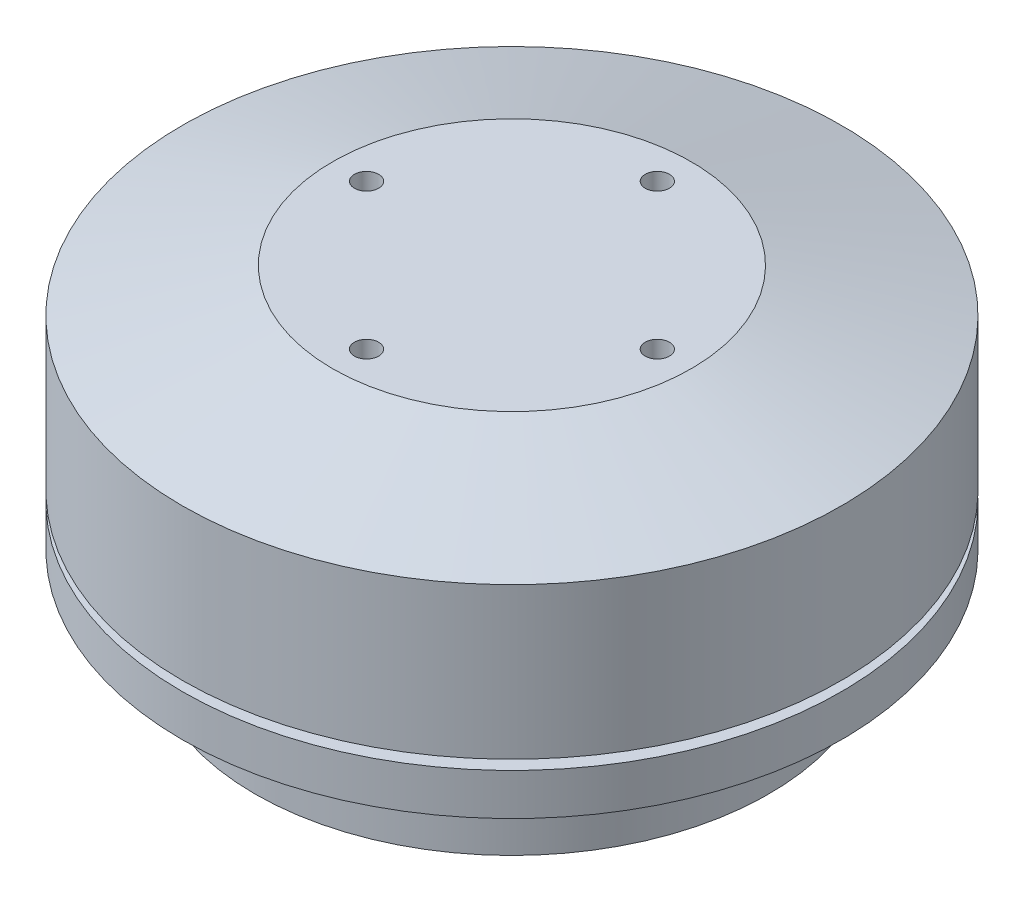
SolidWorks part; units mm, degrees
ref_plane "Спереди" through (0, 0, 0) normal (0, 0, 1) x (1, 0, 0)
ref_plane "Сверху" through (0, 0, 0) normal (0, 1, 0) x (1, 0, 0)
ref_plane "Справа" through (0, 0, 0) normal (1, 0, 0) x (0, 0, -1)
ref_axis "Axis1" through (0, 0, 0) along (0, 1, 0)
sketch "Sketch1" plane through (0, 0, 0) normal (0, 0, 1) x (1, 0, 0)
  line L0 (0, 0) -> (0, -13241.6823) construction
  line L1 (0, 0) -> (0, 34)
  line L2 (0, 34) -> (-18.5, 34)
  line L3 (-18.5, 34) -> (-34, 29.5)
  line L4 (-34, 29.5) -> (-34, 13.9)
  line L5 (-34, 13.9) -> (-32.5205, 13.9)
  line L6 (-32.5205, 13.9) -> (-32.5205, 12.9)
  line L7 (-32.5205, 12.9) -> (-34, 12.9)
  line L8 (-34, 12.9) -> (-34, 8.6)
  line L9 (-34, 8.6) -> (-26.5, 5.6)
  line L10 (-26.5, 5.6) -> (-26.5, 0)
  line L11 (-26.5, 0) -> (0, 0)
  dimension "D1" = 1
  dimension "D2" = 68
  dimension "D3" = 37
  dimension "D4" = 4.5
  dimension "D5" = 4.3
  dimension "D6" = 3
  dimension "D7" = 5.6
  dimension "D8" = 34
  dimension "D9" = 53
revolve "Revolve1" add sketch "Sketch1" angle 360 about L0
hole_wizard "M3x0.5 Tapped Hole1" positions "Sketch2" profile "Sketch3" tap size "M3x0.5" standard "ANSI Metric"
sketch "Sketch2" plane through (0, 34, 0) normal (0, 1, 0) x (1, 0, 0)
  circle A0 centre (0, 0) radius 15 construction
  point P0 (0, 15)
  point P8 (-15, 0)
  point P10 (15, 0)
  point P12 (0, -15)
  dimension "D1" = 30
sketch "Sketch3" plane through (0, 34, -15) normal (1, 0, 0) x (0, 0, 1)
  line L0 (0, 0) -> (0, 6.7511)
  line L1 (0, 6.7511) -> (1.25, 6)
  line L2 (1.25, 6) -> (1.25, 0)
  line L5 (1.25, 0) -> (0, 0)
  line L10 (0, 6.7511) -> (-1.25, 6) construction
  line L11 (0, -6.35) -> (0, 107.95) construction
  dimension "Tap Drill Dia." = 2.5
  dimension "Tap Drill Depth" = 6
  dimension "Drill Angle" = 118
cosmetic thread "Hole Thread1" parameters "D1"=6, "D2"=3
cosmetic thread "Hole Thread2" parameters "D1"=6, "D2"=3
cosmetic thread "Hole Thread3" parameters "D1"=6, "D2"=3
cosmetic thread "Hole Thread4" parameters "D1"=6, "D2"=3
hole_wizard "M3x0.5 Tapped Hole2" positions "Sketch4" profile "Sketch5" tap size "M3x0.5" standard "ANSI Metric"
sketch "Sketch4" plane through (0, 0, 0) normal (0, -1, 0) x (-1, 0, 0)
  circle A0 centre (0, 0) radius 15 construction
  point P0 (0, 15)
  point P8 (0, -15)
  point P10 (15, 0)
  point P12 (-15, 0)
  dimension "D1" = 30
sketch "Sketch5" plane through (0, 0, -15) normal (1, 0, 0) x (0, 0, -1)
  line L0 (0, 0) -> (0, 9.2511)
  line L1 (0, 9.2511) -> (1.25, 8.5)
  line L2 (1.25, 8.5) -> (1.25, 0)
  line L5 (1.25, 0) -> (0, 0)
  line L10 (0, 9.2511) -> (-1.25, 8.5) construction
  line L11 (0, -6.35) -> (0, 107.95) construction
  dimension "Tap Drill Dia." = 2.5
  dimension "Tap Drill Depth" = 8.5
  dimension "Drill Angle" = 118
cosmetic thread "Hole Thread5" parameters "D1"=6, "D2"=3
cosmetic thread "Hole Thread6" parameters "D1"=6, "D2"=3
cosmetic thread "Hole Thread7" parameters "D1"=6, "D2"=3
cosmetic thread "Hole Thread8" parameters "D1"=6, "D2"=3
